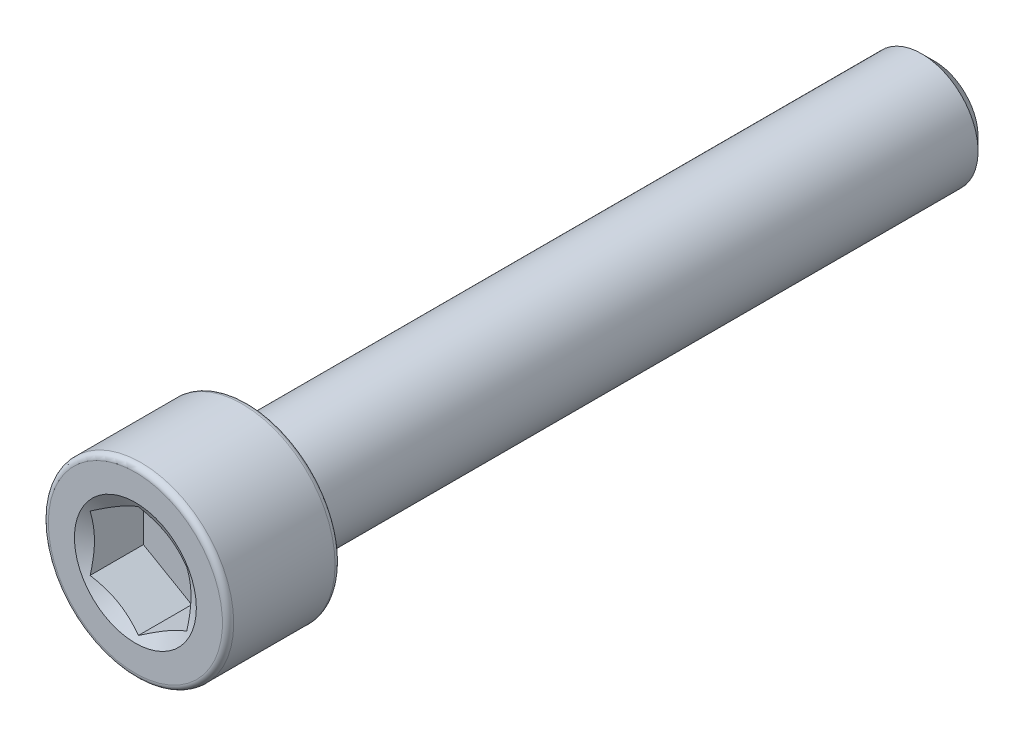
SolidWorks part; units mm, degrees
material "Alloy Steel (SS)"
ref_plane "Front Plane" through (0, 0, 0) normal (0, 0, 1) x (1, 0, 0)
ref_plane "Top Plane" through (0, 0, 0) normal (0, 1, 0) x (1, 0, 0)
ref_plane "Right Plane" through (0, 0, 0) normal (1, 0, 0) x (0, 0, -1)
sketch "Sketch1" plane through (0, 0, 0) normal (1, 0, 0) x (0, 0, -1)
  line L0 (14.7828, 0) -> (-14.7828, 0) construction
  line L1 (-10.6172, 3.429) -> (-10.6172, -3.429) construction
  line L2 (14.7828, 2.0828) -> (14.7828, -2.0828) construction
  line L3 (14.7332, 2.1687) -> (15.1301, 1.4813) construction
  line L4 (15.0805, 1.5672) -> (15.1797, 1.5672) construction
  line L5 (15.1301, 1.4813) -> (15.5269, 2.1687) construction
  line L6 (15.5269, 2.1687) -> (14.7332, 2.1687) construction
  line L7 (15.1301, 1.5672) -> (15.1301, 1.4813) construction
  line L8 (15.1301, 2.1687) -> (15.1301, 2.0828) construction
  line L9 (15.4773, 2.0828) -> (14.7828, 2.0828) construction
  point P4 (-10.6172, 0)
  point P6 (-10.6172, 1.7859)
  point P7 (12.7984, -2.0828)
  point P20 (15.1301, 2.1258)
  dimension "Head Height" = 4.1656
  dimension "Head Diameter" = 6.858
  dimension "Drive Size" = 3.5719
  dimension "Length" = 25.4
  dimension "Screw Size Decimal Equivalent" = 4.1656
  dimension "Pitch" = 0.7937
  dimension "Pitch/8" = 0.0992
  dimension "Thread Note" = 1.9844
sketch "Sketch2" plane through (0, 0, 0) normal (1, 0, 0) x (0, 0, -1)
  line L0 (14.7828, 0) -> (14.7828, 1.6066)
  line L1 (14.7828, 2.0828) -> (14.7828, -2.0828) construction
  line L2 (14.7828, 1.6066) -> (14.3066, 2.0828)
  line L3 (14.3066, 2.0828) -> (-10.6172, 2.0828)
  line L4 (-10.6172, 2.0828) -> (-10.6172, 3.2207)
  line L5 (-10.8255, 3.429) -> (-14.5745, 3.429)
  line L6 (-14.7828, 3.2207) -> (-14.7828, 0)
  line L7 (14.7828, 0) -> (-14.7828, 0) construction
  line L8 (-14.7828, 0) -> (14.7828, 0)
  arc A0 (-10.6172, 3.2207) -> (-10.8255, 3.429) centre (-10.8255, 3.2207) ccw
  arc A1 (-14.5745, 3.429) -> (-14.7828, 3.2207) centre (-14.5745, 3.2207) ccw
  point P19 (-10.6172, 3.429)
  dimension "D3" = 0.2083
  dimension "D1" = 0.4762
  dimension "D2" = 45
revolve "Revolve1" add sketch "Sketch2" angle 360 about L0
sketch "Sketch3" plane through (0, 0, 0) normal (0, 0, 1) x (1, 0, 0)
  line L1 (-1.7859, 1.0311) -> (-1.7859, -1.0311)
  line L2 (-1.7859, -1.0311) -> (0, -2.0622)
  line L3 (0, -2.0622) -> (1.7859, -1.0311)
  line L4 (1.7859, -1.0311) -> (1.7859, 1.0311)
  line L5 (1.7859, 1.0311) -> (0, 2.0622)
  line L6 (0, 2.0622) -> (-1.7859, 1.0311)
  circle A0 centre (0, 0) radius 1.7859 construction
  circle A1 centre (0, 0) radius 3.429 construction
extrude "Cut-Extrude1" cut sketch "Sketch3" against normal blind 2.0828 from vertex starting at point (0, 0, 14.7828)
sketch "Sketch4" plane through (0, 0, 14.7828) normal (0, 0, 1) x (1, 0, 0)
  line L0 (0, 2.0622) -> (0, 2.4484) construction
  line L1 (0, 2.4484) -> (0, 2.8346) construction
  line L2 (0, 2.8346) -> (0, 3.2207) construction
  circle A0 centre (0, 0) radius 2.2553
  point P12 (0, 2.2553)
extrude "Cut-Extrude2" cut sketch "Sketch4" against normal through all draft 60
split "Split1" [suppressed] bodies to split 106 112
sketch "Sketch5" [suppressed] plane through (0, 0, 0) normal (1, 0, 0) x (0, 0, -1)
  line L0 (15.0805, 1.5672) -> (15.1797, 1.5672)
  line L1 (15.1797, 1.5672) -> (15.5021, 2.1258)
  line L2 (15.5021, 2.1258) -> (14.758, 2.1258)
  line L3 (14.758, 2.1258) -> (15.0805, 1.5672)
  line L4 (14.7332, 2.1687) -> (15.1301, 1.4813) construction
sketch "Sketch6" [suppressed] plane through (0, 0, -14.7828) normal (0, 0, -1) x (-1, 0, 0)
  circle A0 centre (0, 0) radius 2.0828
curve "Helix/Spiral1" [suppressed] pitch 0.7937 height 26.1937 turns 33
sweep "Cut-Sweep1" [suppressed] cut profiles "Sketch5" path "Helix/Spiral1"
sketch "Sketch7" [suppressed] plane through (0, 0, 10.6172) normal (0, 0, -1) x (-1, 0, 0)
  circle A0 centre (0, 0) radius 2.1336
  circle A1 centre (0, 0) radius 2.0828 construction
  dimension "D1" = 0.0508
extrude "Boss-Extrude1" [suppressed] add sketch "Sketch7" along normal blind 2.3813 draft 20 and the other way blind 0.4166
ref_plane "Plane1" [suppressed] through (0, 0, 11.9918) normal (0, 0, -1) x (-1, 0, 0)
sketch "Sketch13" [suppressed] plane through (0, 0, 11.9918) normal (0, 0, -1) x (-1, 0, 0)
  line L0 (0.0857, 3.4279) -> (0, 0) construction
  line L1 (0, 0) -> (-0.0857, 3.4279) construction
  line L3 (0.0843, 3.3713) -> (0.0857, 3.4279)
  line L6 (-0.0843, 3.3713) -> (-0.0857, 3.4279)
  arc A1 (0.0857, 3.4279) -> (-0.0857, 3.4279) centre (0, 0) ccw
  circle A2 centre (0, 0) radius 3.429 construction
  arc A3 (0.0843, 3.3713) -> (-0.0843, 3.3713) centre (0, 0) ccw
  point P2 (0, 3.429)
  dimension "D3" = 0.0566
  dimension "D1" = 0.1715
extrude "Cut-Extrude3" [suppressed] cut sketch "Sketch13" against normal blind 2.3244
chamfer "Chamfer3" [suppressed] distance 0.0566 angle 60
chamfer "Chamfer4" [suppressed] distance 0.0566 angle 85
pattern_circular "CirPattern2" [suppressed] count 50 over 360 about axis through (0, 0, -14.7828) along (0, 0, 1) of bodies 134
equation "\"Pitch/8@Sketch1\" = \"Pitch@Sketch1\" / 8"
equation "\"Thread Note@Sketch1\"=\"Pitch@Sketch1\" * 2.5"
equation "\"D1@Sketch2\"=\"Pitch@Sketch1\"*.60"
equation "\"D3@Sketch2\"=\"Head Height@Sketch1\"*.05"
equation "\"D1@Cut-Extrude1\" = \"Head Height@Sketch1\" * .5"
equation "\"D3@Helix/Spiral1\" = \"Length@Sketch1\" + \"Pitch@Sketch1\""
equation "\"D4@Helix/Spiral1\" = \"Pitch@Sketch1\""
equation "\"D2@Boss-Extrude1\" = \"Head Height@Sketch1\" * .1"
equation "\"D1\"= \"Screw Size Decimal Equivalent@Sketch1\" * .4"
equation "\"D1@Plane1\"=\"Head Height@Sketch1\" * .33"
equation "\"D1@Cut-Extrude3\"=( \"Head Height@Sketch1\" - \"D1@Plane1\" - \"D3@Sketch2\" )  * .9"
equation "\"D1@Chamfer3\"=\"D3@Sketch13\""
equation "\"D1@Chamfer4\"=\"D3@Sketch13\""
equation "\"D1@CirPattern2\"=( \"Head Diameter@Sketch1\" * pi )  /  ( 2.5*\"D1@Sketch13\" )"
equation "\"D1@Sketch13\"=\"Head Diameter@Sketch1\" * .025"
equation "\"D3@Sketch13\"=\"D1@Sketch13\"*.33"
equation "\"D1@Boss-Extrude1\"=\"Pitch@Sketch1\"*3"
